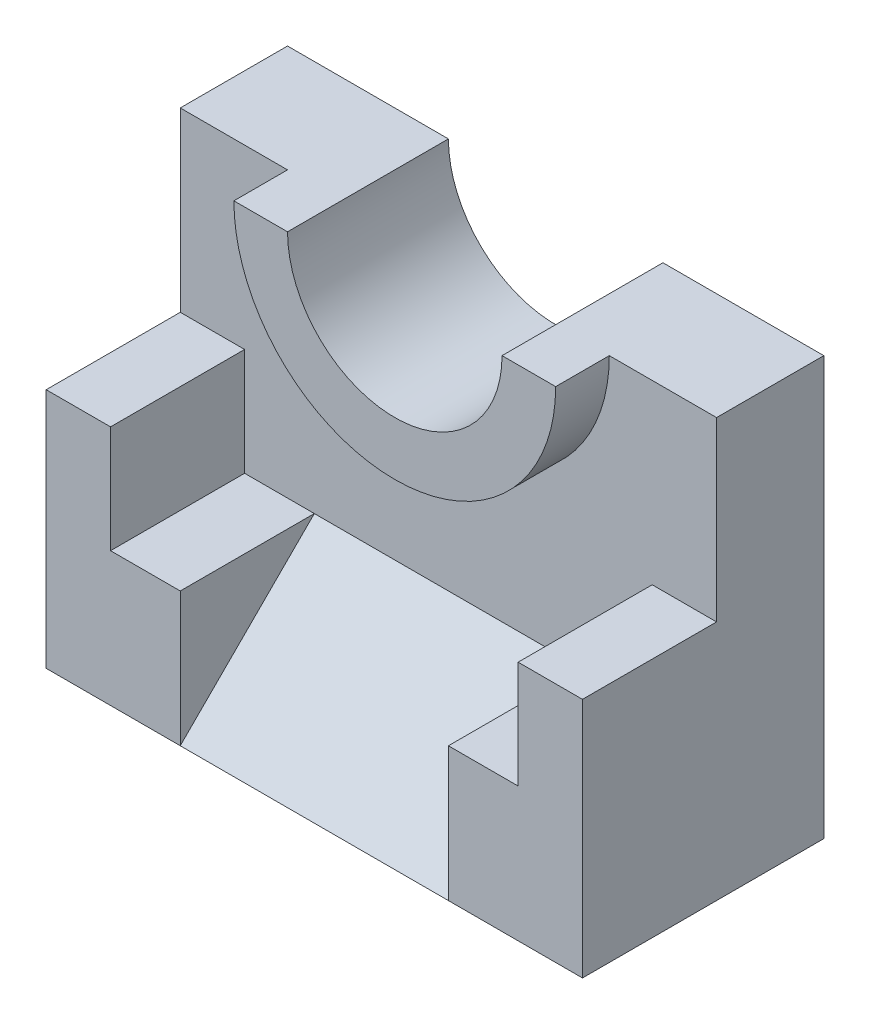
SolidWorks part; units mm, degrees
ref_plane "Front Plane" through (0, 0, 0) normal (0, 0, 1) x (1, 0, 0)
ref_plane "Top Plane" through (0, 0, 0) normal (0, 1, 0) x (1, 0, 0)
ref_plane "Right Plane" through (0, 0, 0) normal (1, 0, 0) x (0, 0, -1)
sketch "Sketch1" plane through (0, 0, 0) normal (0, 0, 1) x (1, 0, 0)
  line L0 (-68.3049, -37.1166) -> (31.6951, -37.1166)
  line L1 (31.6951, -37.1166) -> (31.6951, 40.8834)
  line L2 (31.6951, 40.8834) -> (1.6951, 40.8834)
  line L3 (-68.3049, 40.8834) -> (-68.3049, -37.1166)
  line L4 (-68.3049, -37.1166) -> (-68.3049, 7.8834)
  line L5 (-68.3049, 7.8834) -> (-56.3049, 7.8834)
  line L6 (-56.3049, 7.8834) -> (-56.3049, -12.1166)
  line L7 (-56.3049, -12.1166) -> (-43.3049, -12.1166)
  line L9 (-18.3049, 10.8834) -> (-18.3049, -37.1166) construction
  line L10 (31.6951, 7.8834) -> (19.6951, 7.8834)
  line L11 (19.6951, 7.8834) -> (19.6951, -12.1166)
  line L12 (19.6951, -12.1166) -> (6.6951, -12.1166)
  line L14 (-43.3049, -12.1166) -> (6.6951, -12.1166)
  line L15 (-38.3049, 40.8834) -> (-68.3049, 40.8834)
  arc A0 (-38.3049, 40.8834) -> (1.6951, 40.8834) centre (-18.3049, 40.8834) ccw
  arc A1 (-48.3049, 40.8834) -> (11.6951, 40.8834) centre (-18.3049, 40.8834) ccw
extrude "Boss-Extrude1" add sketch "Sketch1" along normal blind 20 contours L9 A1 L15 L3 L5 L6 L7 L14 | A1 L9 L14 L12 L11 L10 L1 L2 region at (-45.7189, 10.9945, 0) region at (9.1092, 10.9945, 0)
extrude "Boss-Extrude2" add sketch "Sketch1<3>" along normal blind 30 contours L15 A1 L2 A0 region at (-43.3049, 40.2126, 0)
sketch "Sketch1<3>" plane through (0, 0, 0) normal (0, 0, 1) x (1, 0, 0) same geometry as "Sketch1"
extrude "Boss-Extrude6" add sketch "Sketch1<6>" along normal blind 45 contours L14 L9 L0 L1 L10 L11 L12 | L9 L14 L7 L6 L5 L3 L0 region at (-46.3653, -20.9924, 0) region at (9.7555, -20.9924, 0)
sketch "Sketch1<6>" plane through (0, 0, 0) normal (0, 0, 1) x (1, 0, 0) same geometry as "Sketch1"
sketch "Sketch3" plane through (-68.3049, 0, 0) normal (-1, 0, 0) x (0, 0, 1)
  line L0 (45, -37.1166) -> (45, -12.1166)
  line L1 (45, 7.8834) -> (45, -37.1166) construction
  line L2 (45, -12.1166) -> (20, -12.1166)
  line L3 (20, -12.1166) -> (45, -37.1166)
extrude "Cut-Extrude6" cut sketch "Sketch3" against normal blind 140
extrude "Boss-Extrude7" add sketch "Sketch3<2>" against normal blind 25
sketch "Sketch3<2>" plane through (-68.3049, 0, 0) normal (-1, 0, 0) x (0, 0, 1) same geometry as "Sketch3"
ref_plane "Plane1" through (-18.3049, 0, 0) normal (1, 0, 0) x (0, 0, -1)
mirror "Mirror1" about plane through (-18.3049, 0, 0) normal (1, 0, 0) of "Boss-Extrude7"
